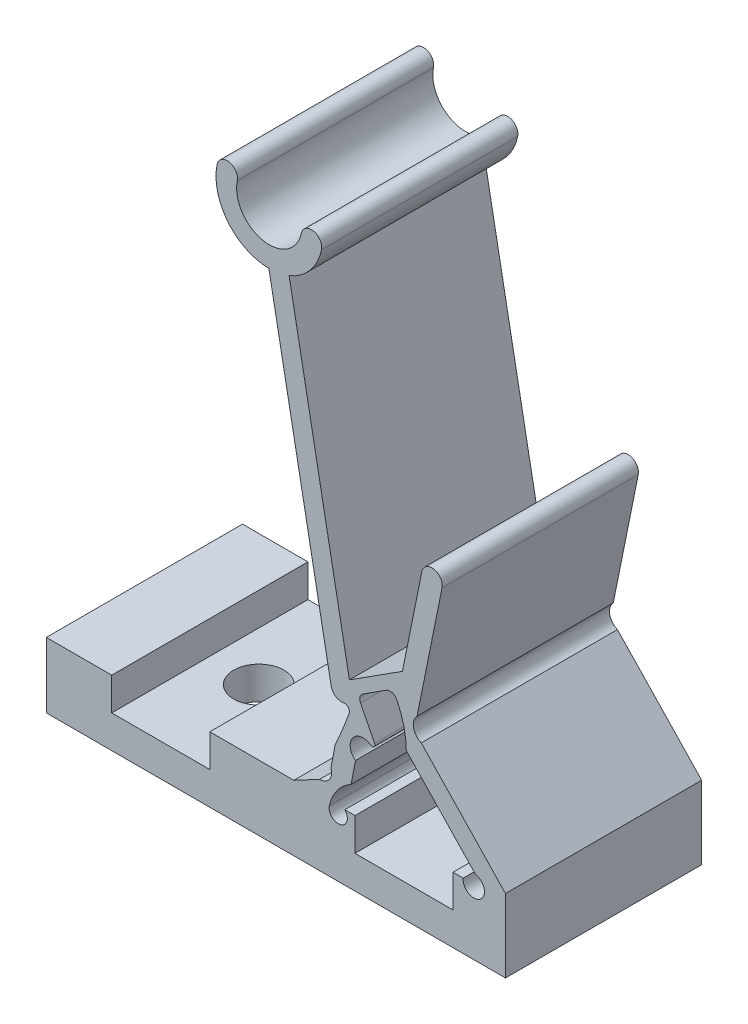
SolidWorks part; units mm, degrees
ref_plane "Front Plane" through (0, 0, 0) normal (0, 0, 1) x (1, 0, 0)
ref_plane "Top Plane" through (0, 0, 0) normal (0, 1, 0) x (1, 0, 0)
ref_plane "Right Plane" through (0, 0, 0) normal (1, 0, 0) x (0, 0, -1)
sketch "Sketch-SkeletonConfigUp" plane through (0, 0, 0) normal (0, 0, 1) x (1, 0, 0)
  line L0 (0, 0) -> (0, -50000) construction
  line L1 (0, 0) -> (7.455, 0.2734) construction
  line L2 (9.9233, 0.3639) -> (10.6101, 4.558) construction
  line L3 (10.6101, 4.558) -> (7.9471, 2.8569) construction
  line L4 (7.9471, 2.8569) -> (7.455, 0.2734) construction
  line L5 (10.6101, 4.558) -> (12.0093, 11.478) construction
  line L6 (7.9471, 2.8569) -> (4.1146, 23.199) construction
  line L7 (7.455, 0.2734) -> (9.9233, 0.3639) construction
  line L8 (-989.4051, -36.2798) -> (9.9233, 0.3639) construction
  dimension "D2" = 7.46
  dimension "D3" = 2.47
  dimension "D4" = 4.25
  dimension "D5" = 78.6
  dimension "D6" = 3.16
  dimension "D7" = 7.06
  dimension "D8" = 20.7
  dimension "D9" = 2.63
  dimension "D10" = 46
  dimension "D11" = 111.9
  dimension "D12" = 92.1
sketch "Sketch-SkeletonConfigDown" plane through (0, 0, 0) normal (0, 0, 1) x (1, 0, 0)
  line L0 (0, 0) -> (0, -50000) construction
  line L1 (0, 0) -> (7.455, 0.2734) construction
  line L2 (9.9233, 0.3639) -> (10.6101, 4.558) construction
  line L3 (10.6101, 4.558) -> (9.7761, 1.5101) construction
  line L4 (9.7761, 1.5101) -> (7.455, 0.2734) construction
  line L5 (10.6101, 4.558) -> (7.0062, 10.6288) construction
  line L6 (9.7761, 1.5101) -> (-6.7111, 14.0265) construction
  line L7 (7.455, 0.2734) -> (9.9233, 0.3639) construction
  line L8 (-993.745, -36.439) -> (9.9233, 0.3639) construction
  dimension "D2" = 7.46
  dimension "D3" = 2.47
  dimension "D4" = 4.25
  dimension "D5" = 78.6
  dimension "D6" = 3.16
  dimension "D7" = 7.06
  dimension "D8" = 20.7
  dimension "D9" = 2.63
  dimension "D10" = 46
  dimension "D11" = 111.9
  dimension "D1" = 92.1
sketch "Sketch-ConfigDown" plane through (0, 0, 0) normal (0, 0, 1) x (1, 0, 0)
  line L3 (7.2122, -0.2359) -> (5.3047, -0.3058) construction
  line L4 (9.7761, 1.5101) -> (-6.7111, 14.0265) construction
  line L6 (-200859.4238, -7365.1807) -> (9.9233, 0.3639) construction
  line L7 (7.2122, -0.2359) -> (15.5786, 0.0709) construction
  line L9 (7.455, 0.2734) -> (9.9233, 0.3639) construction
  line L10 (10.9008, 0.9001) -> (10.9374, -0.0993) construction
  line L15 (9.3493, 0.7161) -> (8.352, 0.1848)
  line L18 (8.512, 1.4031) -> (8.9823, 0.5206) construction
  line L19 (6.5762, 10.3736) -> (9.0074, 6.2784)
  line L20 (-5.3148, 12.3387) -> (8.4132, 1.917)
  line L21 (8.2015, 3.3332) -> (-4.7101, 13.1352)
  line L22 (9.7761, 1.5101) -> (7.455, 0.2734) construction
  line L23 (2.9291, 6.0802) -> (3.5338, 6.8767) construction
  line L26 (10.6101, 4.558) -> (14.4503, 0.5299) construction
  line L27 (10.2553, 5.1557) -> (9.3507, 1.85) construction
  line L28 (11.0112, 4.862) -> (15.5786, 0.0709) construction
  line L29 (14.5562, -0.3058) -> (10.7658, 3.6702) construction
  line L30 (12.9938, 1.3331) -> (13.7176, 2.0231) construction
  line L34 (5.3047, -0.3058) -> (5.3047, -3.4808) construction
  line L36 (5.3047, -3.4808) -> (15.5786, -3.4808)
  line L37 (15.5786, -3.4808) -> (15.5786, 0.0709)
  line L38 (-8.0357, 12.2817) -> (-6.0162, 14.9419) construction
  line L39 (10.6101, 4.558) -> (9.7761, 1.5101) construction
  line L40 (9.7556, 3.3297) -> (10.7202, 3.0657) construction
  line L42 (7.4361, 10.8841) -> (10.4021, 5.8879)
  line L43 (8.1032, 7.8014) -> (8.9631, 8.3119) construction
  line L44 (10.6101, 4.558) -> (7.0062, 10.6288) construction
  line L45 (7.7789, -0.3058) -> (5.3047, -0.3058) construction
  line L46 (14.5562, -0.3058) -> (15.5786, -0.3058) construction
  line L47 (13.528, -0.3058) -> (7.7789, -0.3058)
  line L48 (9.0074, 6.2784) -> (8.2015, 3.3332)
  line L49 (15.5786, 0.0709) -> (15.28, 0.3842)
  line L50 (10.7658, 3.6702) -> (9.7307, 4.7558) construction
  line L51 (15.28, 0.3842) -> (14.5562, -0.3058) construction
  line L52 (14.5815, 0.7545) -> (14.7625, 0.927) construction
  line L53 (13.5212, 0.7799) -> (14.2449, 1.4699) construction
  line L54 (11.0112, 4.862) -> (10.4545, 5.4459) construction
  line L55 (10.7911, 4.7305) -> (10.972, 4.903) construction
  line L56 (9.7307, 4.7558) -> (10.4545, 5.4459) construction
  line L57 (10.7658, 3.6702) -> (11.4896, 4.3602) construction
  line L58 (10.7911, 4.7305) -> (10.4292, 4.3855) construction
  line L59 (11.4896, 4.3602) -> (14.2449, 1.4699)
  line L60 (13.5212, 0.7799) -> (10.7658, 3.6702)
  line L61 (10.4545, 5.4459) -> (10.4021, 5.8879)
  line L62 (7.3374, 0.494) -> (7.2199, 0.7146) construction
  line L63 (7.0282, -0.5206) -> (6.3041, -0.9064) construction
  line L64 (7.8818, 1.0673) -> (8.352, 0.1848) construction
  line L65 (6.558, 0.362) -> (7.0282, -0.5206) construction
  line L66 (6.558, 0.362) -> (5.3047, -0.3058)
  line L67 (6.558, 0.362) -> (7.8818, 1.0673) construction
  line L68 (7.3374, 0.494) -> (7.5725, 0.0527) construction
  line L69 (10.2029, 2.304) -> (10.8079, 2.6264) construction
  line L70 (10.6731, 1.4215) -> (11.1125, 1.6556) construction
  line L71 (9.6585, 1.7307) -> (9.541, 1.9513) construction
  line L72 (8.8791, 1.5987) -> (9.3493, 0.7161) construction
  line L73 (10.2029, 2.304) -> (10.6731, 1.4215) construction
  line L74 (9.6585, 1.7307) -> (9.8936, 1.2894) construction
  line L75 (7.8818, 1.0673) -> (8.8791, 1.5987)
  line L76 (8.4132, 1.917) -> (9.4143, 2.4504)
  line L77 (9.6228, 4.1445) -> (11.1323, 2.561)
  line L78 (11.1323, 2.561) -> (11.3028, 2.3822)
  line L79 (-6.7111, 14.0265) -> (-5.0362, 14.2558) construction
  line L80 (-6.7111, 14.0265) -> (-6.7111, -3.4808) construction
  line L81 (5.3047, -3.4808) -> (-6.7111, -3.4808)
  line L82 (-6.7111, -3.4808) -> (-6.7111, -0.3058)
  line L83 (-6.7111, -0.3058) -> (5.3047, -0.3058)
  line L84 (8.8791, 1.5987) -> (10.2029, 2.304) construction
  arc A2 (-7.4311, 13.0782) -> (-5.5316, 14.188) centre (-6.7111, 14.0265) ccw
  arc A3 (-4.7101, 13.1352) -> (-4.5408, 14.3236) centre (-6.7111, 14.0265) ccw
  arc A4 (-8.0357, 12.2817) -> (-7.4311, 13.0782) centre (-7.7334, 12.68) cw
  arc A5 (-4.5408, 14.3236) -> (-5.5316, 14.188) centre (-5.0362, 14.2558) ccw
  arc A6 (-8.0357, 12.2817) -> (-5.3148, 12.3387) centre (-6.7111, 14.0265) ccw
  arc A7 (6.5762, 10.3736) -> (7.4361, 10.8841) centre (7.0062, 10.6288) cw
  arc A8 (15.28, 0.3842) -> (14.2449, 1.4699) centre (15.4863, 1.6171) cw
  arc A9 (14.5562, -0.3058) -> (13.5212, 0.7799) centre (13.3149, -0.453) ccw
  arc A10 (10.4545, 5.4459) -> (11.4896, 4.3602) centre (11.6958, 5.593) ccw
  arc A11 (9.7307, 4.7558) -> (10.7658, 3.6702) centre (9.5245, 3.523) cw
  arc A12 (7.8818, 1.0673) -> (6.558, 0.362) centre (6.7496, 1.5972) cw
  arc A13 (7.0282, -0.5206) -> (8.352, 0.1848) centre (8.1603, -1.0505) cw
  arc A14 (7.0282, -0.5206) -> (7.7789, -0.3058) centre (7.4971, -0.74) ccw
  arc A15 (8.8791, 1.5987) -> (10.2029, 2.304) centre (9.0707, 2.8339) ccw
  arc A16 (9.3493, 0.7161) -> (10.6731, 1.4215) centre (10.4814, 0.1863) cw
  arc A19 (10.2029, 2.304) -> (9.4143, 2.4504) centre (9.8276, 2.4796) ccw
  arc A20 (14.5562, -0.3058) -> (13.528, -0.3058) centre (14.0421, -0.3668) cw
  arc A21 (9.7307, 4.7558) -> (9.6228, 4.1445) centre (9.6795, 4.4497) ccw
  arc A22 (10.6731, 1.4215) -> (11.3028, 2.3822) centre (10.7698, 2.0448) ccw
  point P24 (8.7471, 0.9618)
  point P28 (10.9191, 0.4004)
  point P30 (8.5332, 8.0566)
  point P43 (10.2379, 3.1977)
  point P47 (14.5815, 0.7545)
  point P51 (3.2315, 6.4785)
  point P61 (13.3557, 1.6781)
  dimension "D1" = 1
  dimension "D8" = 1.5
  dimension "D12" = 1.5
  dimension "D3" = 2.3812
  dimension "D4" = 4.3812
  dimension "D6" = 7
  dimension "D2" = 3.175
  dimension "D7" = 1.5
  dimension "D9" = 1.5
  dimension "D10" = 0.25
  dimension "D11" = 1.5
  dimension "D13" = 0.5
  dimension "D14" = 0.5
  dimension "D15" = 45
sketch "Sketch-ConfigUp" plane through (0, 0, 0) normal (0, 0, 1) x (1, 0, 0)
  line L1 (7.3156, 2.2137) -> (7.1042, 1.1037)
  line L2 (8.0635, 0.796) -> (13.3219, 0.9888) construction
  line L3 (10.1988, -0.1264) -> (6.8464, -0.2493) construction
  line L4 (7.9471, 2.8569) -> (7.455, 0.2734) construction
  line L5 (11.5192, 11.5771) -> (10.5754, 6.909)
  line L6 (7.455, 0.2734) -> (9.9233, 0.3639) construction
  line L7 (10.1988, -0.1264) -> (15.5786, 0.0709) construction
  line L9 (10.6101, 4.558) -> (7.9471, 2.8569) construction
  line L10 (8.9451, 0.8283) -> (8.9817, -0.171) construction
  line L11 (7.2099, 1.6587) -> (8.1922, 1.4716) construction
  line L12 (8.7452, 3.96) -> (9.2835, 3.1173) construction
  line L15 (9.9233, 0.3639) -> (10.6101, 4.558) construction
  line L16 (9.7754, 2.5547) -> (10.7623, 2.3931) construction
  line L17 (12.4994, 11.3789) -> (11.2863, 5.379)
  line L18 (10.6101, 4.558) -> (12.0093, 11.478) construction
  line L19 (10.5058, 6.5648) -> (11.486, 6.3666) construction
  line L20 (4.0933, 20.6116) -> (7.1163, 4.5661)
  line L21 (8.0021, 5.2653) -> (5.076, 20.7968)
  line L22 (7.9471, 2.8569) -> (4.1146, 23.199) construction
  line L23 (6.0985, 9.9681) -> (7.0813, 10.1533) construction
  line L24 (8.3015, 3.6766) -> (10.1621, 4.8651) construction
  line L26 (10.6101, 4.558) -> (14.4503, 0.5299) construction
  line L27 (-200855.0838, -7365.0216) -> (9.9233, 0.3639) construction
  line L30 (10.7658, 3.6702) -> (11.4896, 4.3602) construction
  line L34 (6.8464, -0.2493) -> (6.8464, -3.4808) construction
  line L38 (2.5546, 22.9051) -> (4.1146, 23.199) construction
  line L39 (4.1146, 23.199) -> (6.6472, 22.6686) construction
  line L40 (13.528, -0.3058) -> (7.7789, -0.3058) construction
  line L41 (13.528, -0.3058) -> (7.7789, -0.3058)
  line L42 (11.2489, 5.194) -> (10.7354, 2.6543) construction
  line L43 (10.1621, 4.8651) -> (9.715, 2.6538) construction
  line L44 (6.8464, -0.2493) -> (5.1916, -0.31) construction
  line L45 (8.0635, 0.796) -> (8.0865, 0.9166) construction
  line L46 (8.0635, 0.796) -> (7.8058, -0.5569) construction
  line L47 (7.2094, 0.3201) -> (6.9638, 0.3669) construction
  line L48 (7.2094, 0.3201) -> (7.7006, 0.2266) construction
  line L49 (6.8235, -0.3698) -> (7.8058, -0.5569) construction
  line L50 (7.4382, 2.8574) -> (7.5963, 3.6872) construction
  line L51 (8.3979, 2.5516) -> (8.5786, 3.5001) construction
  line L52 (7.3156, 2.2137) -> (8.2979, 2.0266) construction
  line L53 (7.5963, 3.6872) -> (8.5786, 3.5001) construction
  line L54 (7.7015, 2.9037) -> (8.1927, 2.8101) construction
  line L55 (7.7015, 2.9037) -> (7.4559, 2.9505) construction
  line L56 (8.1564, 2.8991) -> (7.6708, 3.0185) construction
  line L57 (7.1163, 4.5661) -> (7.4382, 2.8574) construction
  line L58 (11.2863, 5.379) -> (10.3061, 5.5772) construction
  line L59 (7.4382, 2.8574) -> (7.3156, 2.2137) construction
  line L60 (7.8068, 2.1202) -> (8.6839, 3.337) construction
  line L61 (8.2979, 2.0266) -> (8.0865, 0.9166)
  line L62 (7.1042, 1.1037) -> (8.0865, 0.9166) construction
  line L67 (4.1146, 23.199) -> (1.5821, 23.7295) construction
  line L69 (10.8552, 4.5085) -> (11.1002, 4.4589) construction
  line L70 (7.7789, -0.3058) -> (5.3047, -0.3058) construction
  line L71 (7.7789, -0.3058) -> (5.3047, -0.3058) construction
  line L73 (7.1042, 1.1037) -> (6.8464, -0.2493) construction
  line L74 (10.2687, 5.3922) -> (11.2489, 5.194) construction
  line L75 (9.9714, 3.922) -> (10.9516, 3.7238) construction
  line L76 (10.8552, 4.5085) -> (10.3651, 4.6076) construction
  line L77 (8.3979, 2.5516) -> (8.2979, 2.0266) construction
  line L78 (9.5833, 3.3088) -> (8.3979, 2.5516) construction
  line L79 (8.0021, 5.2653) -> (10.5754, 6.909)
  line L80 (8.0021, 5.2653) -> (8.3015, 3.6766) construction
  line L81 (10.5058, 6.5648) -> (10.1621, 4.8651) construction
  line L82 (10.5058, 6.5648) -> (10.5754, 6.909) construction
  line L83 (11.4896, 4.3602) -> (10.7658, 3.6702) construction
  line L84 (11.1158, 4.8153) -> (10.6255, 4.7174) construction
  line L106 (6.558, 0.362) -> (5.3047, -0.3058)
  line L107 (5.3047, -0.3058) -> (-6.7111, -0.3058)
  line L108 (-6.7111, -0.3058) -> (-6.7111, -3.4808)
  line L109 (-6.7111, -3.4808) -> (15.5786, -3.4808)
  line L110 (15.5786, -3.4808) -> (15.5786, 0.0709)
  line L112 (15.5786, 0.0709) -> (11.4896, 4.3602)
  line L114 (11.1277, 4.0152) -> (10.7962, 5.4781) construction
  line L115 (9.5833, 3.3088) -> (10.5323, 3.915) construction
  line L116 (13.3219, 0.9888) -> (10.7658, 3.6702)
  line L117 (10.7658, 3.6702) -> (10.5323, 3.915) construction
  line L118 (10.6101, 4.558) -> (7.9471, 2.8569) construction
  line L119 (8.6839, 3.337) -> (9.4161, 2.8092) construction
  line L120 (8.6839, 3.337) -> (7.8068, 3.9692) construction
  line L121 (9.0288, 3.0406) -> (8.2979, 2.0266) construction
  line L123 (9.7888, 5.7212) -> (8.6571, 4.9983)
  line L124 (8.5388, 4.5661) -> (9.2253, 3.2085)
  line L126 (13.3219, 0.9888) -> (14.1275, 0.1438)
  line L127 (11.2489, 5.194) -> (11.2863, 5.379) construction
  arc A0 (11.5192, 11.5771) -> (12.4994, 11.3789) centre (12.0093, 11.478) cw
  arc A2 (2.5609, 23.5245) -> (5.6684, 22.8736) centre (4.1146, 23.199) ccw
  arc A3 (5.076, 20.7968) -> (6.6472, 22.6686) centre (4.1146, 23.199) ccw
  arc A4 (1.5821, 23.7295) -> (2.5609, 23.5245) centre (2.0715, 23.627) cw
  arc A5 (6.6472, 22.6686) -> (5.6684, 22.8736) centre (6.1578, 22.7711) ccw
  arc A6 (1.5821, 23.7295) -> (4.0933, 20.6116) centre (4.1146, 23.199) ccw
  arc A7 (13.528, -0.3058) -> (14.5562, -0.3058) centre (14.0421, -0.3668) ccw construction
  arc A8 (13.528, -0.3058) -> (14.1275, 0.1438) centre (14.0421, -0.3668) ccw
  arc A9 (7.1042, 1.1037) -> (6.8235, -0.3698) centre (5.9815, 0.554) cw construction
  arc A10 (7.8058, -0.5569) -> (8.0865, 0.9166) centre (8.9285, -0.0073) cw construction
  arc A11 (7.3156, 2.2137) -> (7.5963, 3.6872) centre (6.4736, 3.1376) ccw construction
  arc A12 (8.2979, 2.0266) -> (8.5786, 3.5001) centre (9.4206, 2.5762) cw construction
  arc A13 (11.2489, 5.194) -> (10.9516, 3.7238) centre (12.0804, 4.2607) ccw construction
  arc A14 (10.2687, 5.3922) -> (9.9714, 3.922) centre (9.1399, 4.8553) cw construction
  arc A15 (8.0865, 0.9166) -> (7.0282, -0.5206) centre (9.1391, -0.9668) ccw
  arc A16 (7.1042, 1.1037) -> (6.558, 0.362) centre (6.5823, 0.916) cw
  arc A17 (7.0282, -0.5206) -> (7.7789, -0.3058) centre (7.4604, -0.612) ccw
  arc A18 (11.4896, 4.3602) -> (11.2863, 5.379) centre (11.7287, 4.9376) cw
  arc A19 (8.2979, 2.0266) -> (9.0288, 3.0406) centre (8.6634, 2.5336) cw
  arc A21 (7.3156, 2.2137) -> (7.9864, 3.8397) centre (-8.9784, 9.887) ccw
  arc A22 (7.9864, 3.8397) -> (7.7104, 4.1617) centre (7.7563, 3.9218) ccw
  arc A23 (10.7658, 3.6702) -> (10.3061, 5.5772) centre (6.3229, 3.6081) ccw
  arc A24 (7.7104, 4.1617) -> (7.1163, 4.5661) centre (7.615, 4.66) cw
  arc A25 (9.0288, 3.0406) -> (9.2253, 3.2085) centre (9.1066, 3.1485) ccw
  arc A27 (10.3061, 5.5772) -> (9.7888, 5.7212) centre (9.9829, 5.4174) ccw
  arc A39 (8.6571, 4.9983) -> (8.5388, 4.5661) centre (8.8369, 4.7168) ccw
  point P6 (1.5719, 22.72)
  point P25 (9.0144, 3.5387)
  point P27 (7.701, 1.5651)
  point P28 (8.9634, 0.3287)
  point P36 (10.2689, 2.4739)
  point P38 (10.9959, 6.4657)
  point P51 (6.5899, 10.0607)
  point P61 (11.1277, 4.0152)
  point P65 (1.5719, 22.72)
  point P71 (1.5719, 22.72)
  point P82 (0, 0)
  point P86 (1.5719, 22.72)
  point P107 (1.5719, 22.72)
  point P120 (0, 0)
  point P123 (1.5821, 23.7295)
  point P126 (2.5546, 23.4494)
  point P127 (0, 0)
  dimension "D3" = 3.175
  dimension "D4" = 5.175
  dimension "D13" = 0.625
  dimension "D17" = 0.625
  dimension "D1" = 1
  dimension "D5" = 7
  dimension "D10" = 1.5
  dimension "D11" = 0.25
  dimension "D8" = 1.5
  dimension "D9" = 0.25
  dimension "D6" = 1.5
  dimension "D7" = 0.25
  dimension "D12" = 1.5
  dimension "D15" = 0.5
  dimension "D16" = 1.5
  dimension "D18" = 0.5
  dimension "D19" = 25
  dimension "D20" = 1.5
  dimension "D14" = 22.5
  dimension "D21" = 22.5
extrude "Boss-ConfigUp" add sketch "Sketch-ConfigUp" along normal blind 9.525
sketch "Sketch2" plane through (0.0043, -0.3058, 0) normal (0, -1, 0) x (-1, 0, 0)
  line L1 (-13.0304, 0) -> (-8.2679, 0)
  line L2 (-13.0304, 0) -> (-13.0304, -9.525)
  line L3 (-13.0304, -9.525) -> (-8.2679, -9.525)
  line L4 (-8.2679, 0) -> (-8.2679, -9.525)
  line L5 (-13.5237, 0) -> (-13.0304, 0) construction
  line L7 (-8.2679, 0) -> (-7.7746, 0) construction
  line L10 (-15.5743, -4.7625) -> (6.7155, -4.7625) construction
  line L12 (-13.0304, 0) -> (-8.2679, -9.525) construction
  line L17 (-13.0304, -9.525) -> (-8.2679, 0) construction
  line L18 (6.7155, 0) -> (-15.5743, 0) construction
  line L19 (6.7155, -9.525) -> (6.7155, 0) construction
  line L20 (3.5405, -9.525) -> (3.5405, 0)
  line L21 (3.5405, -9.525) -> (-1.222, -9.525)
  line L22 (3.5405, 0) -> (-1.222, 0)
  line L23 (-1.222, -9.525) -> (-1.222, 0)
  line L24 (3.5405, -9.525) -> (-1.222, 0) construction
  line L25 (3.5405, 0) -> (-1.222, -9.525) construction
  line L26 (6.7155, -9.525) -> (-15.5743, -9.525) construction
  line L27 (-15.5743, -9.525) -> (-15.5743, 0) construction
  point P4 (-10.6492, -4.7625)
  point P26 (1.1592, -4.7625)
  dimension "D1" = 4.7625
  dimension "D2" = 3.175
extrude "Cut-NutSlot" cut sketch "Sketch2" along normal blind 1.5875
hole_wizard "#2 Clearance Hole1" positions "Sketch4" profile "Sketch3" hole size "#2" standard "ANSI Inch" end condition up to next
sketch "Sketch4" plane through (0, -3.4808, 0) normal (0, -1, 0) x (-1, 0, 0)
  line L16 (-13.0347, 0) -> (-8.2722, -9.525) construction
  point P40 (-10.6535, -4.7625)
  point P44 (1.1549, -4.7625)
sketch "Sketch3" plane through (10.6535, -3.4808, 4.7625) normal (1, 0, 0) x (0, 0, -1)
  line L0 (0, 0) -> (0, 1.5875)
  line L1 (0, 1.5875) -> (1.2192, 1.5875)
  line L2 (1.2192, 1.5875) -> (1.2192, 0)
  line L5 (1.2192, 0) -> (0, 0)
  line L11 (0, -6.35) -> (0, 107.95) construction
  dimension "Thru Hole Dia." = 2.4384
  dimension "Thru Hole Depth" = 1.5875
ref_plane "Plane-Midplane" through (0, 0, 4.7625) normal (0, 0, -1) x (-1, 0, 0)
equation "\"axle-diameter\"=2"
equation "\"switch-thickness\"=12"
equation "\"base-width\"=4.0"
equation "\"axle-bushing-radius\"=3"
equation "\"clearance\"= 0.25"
equation "\"arm-width\"=1.0"
equation "\"min-diameter\"=70"
equation "\"alpha\"=92.1"
equation "\"beta\"=26.0"
equation "\"gamma\"=78.6"
equation "\"delta\"=111.9"
equation "\"epsilon\"=46.0"
equation "\"eta\"=-228.1"
equation "\"l_AB\"=2.47"
equation "\"l_AC\"=2.63"
equation "\"l_BD\"=4.25"
equation "\"l_CD\"=3.16"
equation "\"l_CE\"=20.70"
equation "\"l_DF\"=7.06"
equation "\"l_OA\"=7.46"
equation "\"D2@Sketch-SkeletonConfigUp\" = \"l_OA\""
equation "\"D3@Sketch-SkeletonConfigUp\" = \"l_AB\""
equation "\"D4@Sketch-SkeletonConfigUp\" = \"l_BD\""
equation "\"D5@Sketch-SkeletonConfigUp\" = \"gamma\""
equation "\"D6@Sketch-SkeletonConfigUp\" = \"l_CD\""
equation "\"D7@Sketch-SkeletonConfigUp\" = \"l_DF\""
equation "\"D8@Sketch-SkeletonConfigUp\" = \"l_CE\""
equation "\"D9@Sketch-SkeletonConfigUp\" = \"l_AC\""
equation "\"D_groove\"=3.175"
equation "\"D3@Sketch-ConfigUp\" = \"D_groove\""
equation "\"D4@Sketch-ConfigUp\" = \"D_groove\" + 2 * \"arm-width\""
equation "\"D7@Sketch-SkeletonConfigDown\" = \"l_DF\""
equation "\"D6@Sketch-SkeletonConfigDown\" = \"l_CD\""
equation "\"D2@Sketch-SkeletonConfigDown\" = \"l_OA\""
equation "\"D3@Sketch-SkeletonConfigDown\" = \"l_AB\""
equation "\"D9@Sketch-SkeletonConfigDown\" = \"l_AC\""
equation "\"D8@Sketch-SkeletonConfigDown\" = \"l_CE\""
equation "\"D5@Sketch-SkeletonConfigDown\" = \"gamma\""
equation "\"D4@Sketch-SkeletonConfigDown\" = \"l_BD\""
equation "\"D1@Sketch-SkeletonConfigDown\" = \"alpha\""
equation "\"D5@Sketch-ConfigDown\" = \"arm-width\""
equation "\"hinge_length\"=1.5"
equation "\"hinge_depth\"=0.25"
equation "\"D9@Sketch-ConfigDown\" = \"hinge_length\""
equation "\"D10@Sketch-ConfigDown\" = \"hinge_depth\""
equation "\"D8@Sketch-ConfigDown\" = \"hinge_length\""
equation "\"D11@Sketch-ConfigDown\" = \"hinge_length\""
equation "\"D12@Sketch-ConfigDown\" = \"hinge_length\""
equation "\"D10@Sketch-ConfigUp\" = \"hinge_length\""
equation "\"D11@Sketch-ConfigUp\" = \"hinge_depth\""
equation "\"D8@Sketch-ConfigUp\" = \"hinge_length\""
equation "\"D9@Sketch-ConfigUp\" = \"hinge_depth\""
equation "\"D6@Sketch-ConfigUp\" = \"hinge_length\""
equation "\"D7@Sketch-ConfigUp\" = \"hinge_depth\""
equation "\"D10@Sketch-SkeletonConfigUp\"=\"epsilon\""
equation "\"D11@Sketch-SkeletonConfigUp\"=\"delta\""
equation "\"D12@Sketch-SkeletonConfigUp\"=\"alpha\""
equation "\"D11@Sketch-SkeletonConfigDown\"=\"delta\""
equation "\"D10@Sketch-SkeletonConfigDown\"=\"epsilon\""
equation "\"D15@Sketch-ConfigUp\"=2*\"hinge_depth\""
equation "\"D16@Sketch-ConfigUp\"=\"hinge_length\""
equation "\"D18@Sketch-ConfigUp\"=2*\"hinge_depth\""
equation "\"D20@Sketch-ConfigUp\"=\"hinge_length\""
